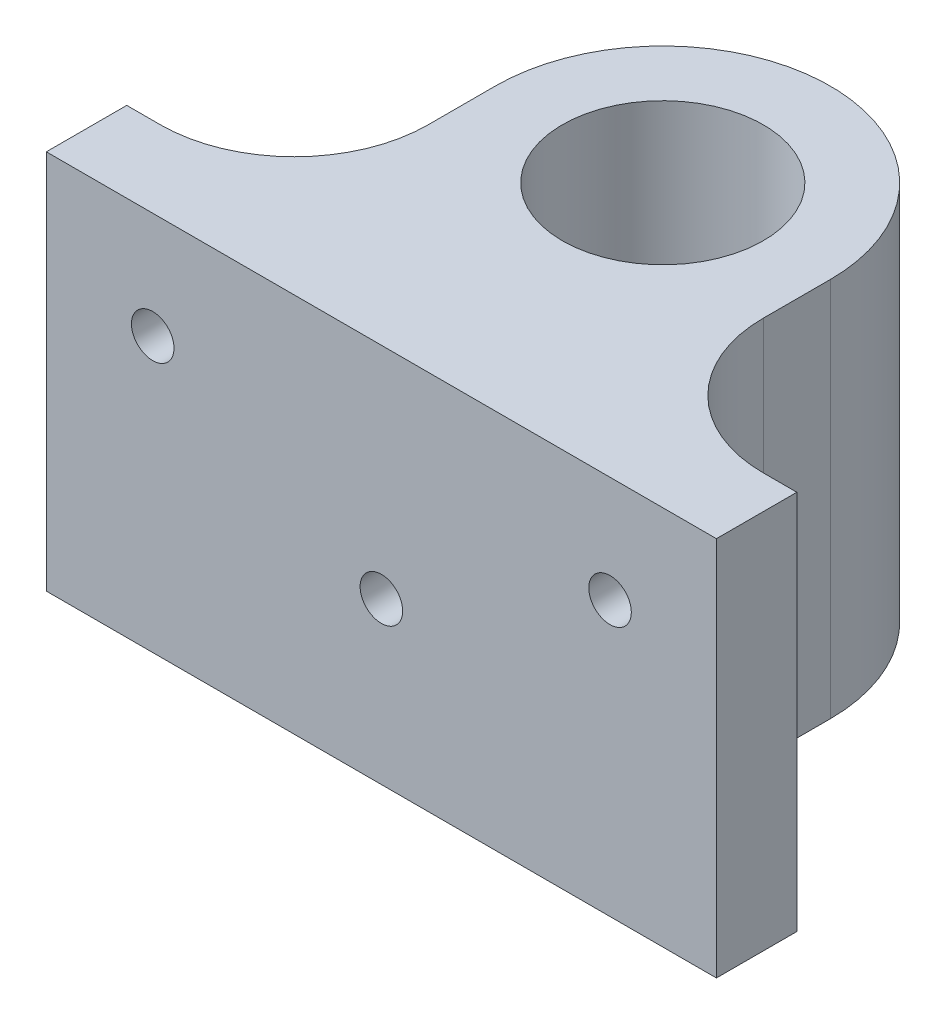
SolidWorks part; units mm, degrees
ref_plane "Front Plane" through (0, 0, 0) normal (0, 0, 1) x (1, 0, 0)
ref_plane "Top Plane" through (0, 0, 0) normal (0, 1, 0) x (1, 0, 0)
ref_plane "Right Plane" through (0, 0, 0) normal (1, 0, 0) x (0, 0, -1)
sketch "Profile-Sketch1" plane through (0, 0, 0) normal (0, 1, 0) x (1, 0, 0)
  line L0 (-25, -21) -> (25, -21)
  line L1 (25, -21) -> (25, -15)
  line L2 (-25, -21) -> (-25, -15)
  line L3 (-25, -15) -> (-22.5, -15)
  line L4 (-12.5, -5) -> (-12.5, 0)
  line L5 (25, -15) -> (22.5, -15)
  line L6 (12.5, -5) -> (12.5, 0)
  circle A0 centre (0, 0) radius 7.5
  arc A6 (12.5, 0) -> (-12.5, 0) centre (0, 0) ccw
  arc A7 (22.5, -15) -> (12.5, -5) centre (22.5, -5) cw
  arc A8 (-12.5, -5) -> (-22.5, -15) centre (-22.5, -5) cw
  dimension "D1" = 15
  dimension "D2" = 12.5
  dimension "D7" = 10
  dimension "D3" = 50
  dimension "D4" = 25
  dimension "D5" = 21
  dimension "D6" = 6
extrude "Profile-Boss-Extrude2" add sketch "Profile-Sketch1" along normal blind 28.3901
sketch "FasteningHoleSketch3" plane through (0, 0, 21) normal (0, 0, 1) x (1, 0, 0)
  line L0 (25, 28.3901) -> (25, 0) construction
  line L1 (-25, 28.3901) -> (-25, 0) construction
  line L2 (-25, 0) -> (25, 0) construction
  circle A2 centre (-17.0625, 20.4526) radius 1.5875
  circle A3 centre (17.0625, 20.4526) radius 1.5875
  dimension "D3" = 3.175
  dimension "D6" = 7.9375
  dimension "D2" = 20.4526
  dimension "D1" = 7.9375
extrude "FasteningHoleCut-Extrude8" cut sketch "FasteningHoleSketch3" against normal through all
sketch "LM8UUFasteningHoleSketch5" plane through (0, 0, 21) normal (0, 0, 1) x (1, 0, 0)
  line L0 (25, 28.3901) -> (25, 0) construction
  line L1 (-25, 0) -> (25, 0) construction
  line L2 (-25, 28.3901) -> (25, 28.3901) construction
  circle A0 centre (0, 12) radius 1.5875
  circle A1 centre (-17.0625, 20.4526) radius 1.5875 construction
  dimension "D1" = 25
  dimension "D2" = 12
  dimension "D3" = 16.3901
extrude "LM8UUFasteningHoleCut-Extrude9" cut sketch "LM8UUFasteningHoleSketch5" against normal through all
equation "\"RailThickness\"= .125in'Spec"
equation "\"LM8UUDiameter\"= 15mm"
equation "\"MidLeftOrRightSideRailHeight\"= 2.0in"
equation "\"RodStabilizerLength\"= 50mm"
equation "\"HoleOffsetFromEdge\"= \"RailThickness\" * 2.5"
equation "\"StepperMountingHoleOffsetFromItsSide\"= 5.5mm'Spec"
equation "\"StepperMountingHoleOffsetFromLeftOrRightSide\"= \"StepperMountingHoleOffsetFromItsSide\" + \"RailThickness\""
equation "\"StepperMountingHoleDistance\"= 31mm'Spec"
equation "\"LM8UUHeight\"= 24mm'Spec"
equation "\"ZAxisLeadScrewLength\"= 200mm"
equation "\"LegHeight\"= 70mm'Space needed for PSU/Stepper/Electronics"
equation "\"V1 BottomOfLowerRail\"= \"LegHeight\""
equation "\"StepperShaftLength\"= 24mm'Pulley will be attached to the end"
equation "\"V2 ToBedAtTopOfZAxis\"= \"V1 BottomOfLowerRail\" - \"LowerEnclosureThickness\" + \"StepperShaftLength\" + \"ZAxisLeadScrewLength\" - \"LM8UUHeight\" / 2"
equation "\"HotEndToTopOfXAxisGB\"= 63.315144mm'Measured from the100.Should be 63.315144"
equation "\"TopOfGBToBottomOfLinearRail\"= \"LinearGBWidth\" / 2 + \"LinearRailWidth\" / 2"
equation "\"LinearGBWidth\"= 27mm'Spec"
equation "\"V5 ToBottomOfXAxisLinearRail\"= \"V4 ToTopOfBuildPlate/HotEndTip\" + \"HotEndToTopOfXAxisGB\" - \"TopOfGBToBottomOfLinearRail\""
equation "\"LinearRailWidth\"= 12mm'Spec"
equation "\"V6 ToMiddleOfYAxisGantryBlock\"= \"V5 ToBottomOfXAxisLinearRail\" - \"GABHeight\" / 2'Equals 325.31514"
equation "\"GABUpperHeight\"= 6mm"
equation "\"GABMidWallHeight\"= 28mm'Must equal 28 or changes alignment"
equation "\"BedToBuildPlateStandoffLength\"= 15mm"
equation "\"BuildPlateHeight\"= 8mm'Spec"
equation "\"V4 ToTopOfBuildPlate/HotEndTip\"= \"V2 ToBedAtTopOfZAxis\" + \"BedToBuildPlateStandoffLength\" + \"BuildPlateHeight\""
equation "\"FasteningHoleDiameter\"= .125in"
equation "\"RodStabilizerHeight\"= \"V8 ToBottomOfMidSideRail\" - \"V2 ToBedAtTopOfZAxis\" + \"HoleOffsetFromEdge\" * 2"
equation "\"LowerEnclosureThickness\"= 5mm"
equation "\"D1@Profile-Sketch1\" = \"LM8UUDiameter\""
equation "\"D3@Profile-Sketch1\" = \"RodStabilizerLength\""
equation "\"D4@Profile-Sketch1\" = \"RodStabilizerLength\" / 2"
equation "\"RodStabilizerWidthFromMidRailToZAxisRodCenter\"= \"StepperMountingHoleOffsetFromLeftOrRightSide\" + \"StepperMountingHoleDistance\" / 2 - \"RailThickness\""
equation "\"StandardWallThickness\"= 3mm"
equation "\"D6@Profile-Sketch1\" = \"StandardWallThickness\" * 2"
equation "\"D1@Profile-Boss-Extrude2\"= \"RodStabilizerHeight\""
equation "\"D6@FasteningHoleSketch3\"=\"HoleOffsetFromEdge\""
equation "\"D2@LM8UUFasteningHoleSketch5\"=\"LM8UUHeight\"/2"
equation "\"V8 ToTopOfMidSideRail\" = \"V6 ToMiddleOfYAxisGantryBlock\" + \"MidSideRailVerticalOffset\""
equation "\"D5@Profile-Sketch1\"=\"RodStabilizerWidthFromMidRailToZAxisRodCenter\""
equation "\"RodStabilizerMountingHoleYOffsetFromBottom\"= \"RodStabilizerHeight\" - \"HoleOffsetFromEdge\""
equation "\"D2@FasteningHoleSketch3\"=\"RodStabilizerMountingHoleYOffsetFromBottom\""
equation "\"D3@FasteningHoleSketch3\"=\"FasteningHoleDiameter\""
equation "\"GABLowerHeight\"= 3mm"
equation "\"GABHeight\"= \"GABLowerHeight\" + \"GABMidWallHeight\" + \"GABUpperHeight\""
equation "\"V8 ToBottomOfMidSideRail\"= \"V8 ToTopOfMidSideRail\" - \"MidLeftOrRightSideRailHeight\"'Equals 289.51514"
equation "\"D1@LM8UUFasteningHoleSketch5\"=\"RodStabilizerLength\"/2"
equation "\"MidSideRailVerticalOffset\"= \"LinearRailWidth\" + 3mm'Allows space for RodStabilizer to attach to bottom of MidSideRail"
